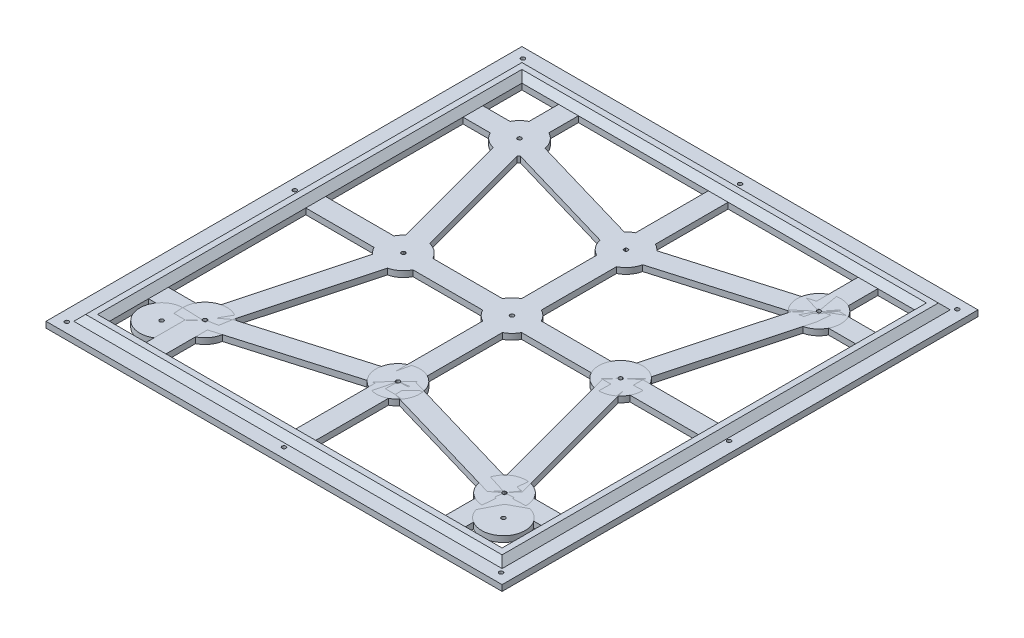
SolidWorks part; units mm, degrees
ref_plane "Front Plane" through (0, 0, 0) normal (0, 0, 1) x (1, 0, 0)
ref_plane "Top Plane" through (0, 0, 0) normal (0, 1, 0) x (1, 0, 0)
ref_plane "Right Plane" through (0, 0, 0) normal (1, 0, 0) x (0, 0, -1)
sketch "Sketch1" plane through (0, 0, 0) normal (0, 1, 0) x (1, 0, 0)
  line L1 (-115, 120) -> (115, 120)
  line L2 (-115, 120) -> (-115, -120)
  line L3 (-115, -120) -> (115, -120)
  line L4 (115, 120) -> (115, -120)
  line L5 (-115, 120) -> (115, -120) construction
  line L6 (-115, -120) -> (115, 120) construction
  point P0 (0, 0)
  dimension "D1" = 240
  dimension "D2" = 230
extrude "Boss-Extrude1" add sketch "Sketch1" along normal blind 3
sketch "Sketch2" plane through (0, 3, 0) normal (0, 1, 0) x (1, 0, 0)
  line L0 (0, -115) -> (0, 0) construction
  line L5 (-109.5, 115) -> (109.5, 115) construction
  line L7 (-109.5, 115) -> (-109.5, -115) construction
  line L8 (-109.5, -115) -> (109.5, -115) construction
  line L9 (115, -120) -> (115, 120)
  line L11 (115, 120) -> (-115, 120)
  line L13 (-115, 120) -> (-115, -120)
  line L15 (-115, -120) -> (115, -120)
  line L16 (115, -120) -> (115, 120) construction
  line L17 (115, 120) -> (-115, 120) construction
  line L18 (-115, 120) -> (-115, -120) construction
  line L19 (-115, -120) -> (115, -120) construction
  line L20 (109.5, 115) -> (109.5, -115) construction
  line L21 (-109.5, 115) -> (109.5, -115) construction
  line L22 (-109.5, -115) -> (109.5, 115) construction
  line L23 (-109.5, 0) -> (0, 0) construction
  line L24 (0, 0) -> (109.5, 0) construction
  line L25 (0, 0) -> (0, 115) construction
  circle A0 centre (0, 0) radius 125 construction
  circle A1 centre (-109.5, -115) radius 1
  circle A2 centre (109.5, -115) radius 1
  circle A3 centre (0, -115) radius 1
  circle A4 centre (-86.1971, -90.5266) radius 1
  circle A5 centre (86.1971, -90.5266) radius 1
  circle A6 centre (0, 0) radius 1
  circle A7 centre (-109.5, 0) radius 1
  circle A8 centre (-109.5, 115) radius 1
  circle A9 centre (-75.5086, 79.3013) radius 1
  circle A10 centre (75.5086, 79.3013) radius 1
  circle A11 centre (0, 115) radius 1
  circle A12 centre (109.5, 115) radius 1
  circle A13 centre (109.5, 0) radius 1
  circle A14 centre (0, 57.5) radius 1
  circle A15 centre (0, -57.5) radius 1
  circle A16 centre (-54.75, 0) radius 1
  circle A17 centre (54.75, 0) radius 1
  circle A19 centre (0, 0) radius 109.5 construction
  circle A20 centre (-75.5086, -79.3013) radius 1
  circle A21 centre (75.5086, -79.3013) radius 1
  point P2 (0, 0)
  point P46 (0, 0)
  point P47 (0, 0)
  dimension "D1" = 0
  dimension "D2" = 219
  dimension "D3" = 5
  dimension "D4" = 2
  dimension "D5" = 240
  dimension "D6" = 24.4734
  dimension "D7" = 250
extrude "Cut-Extrude1" cut sketch "Sketch2" against normal up to next
sketch "Sketch4" plane through (0, 3, 0) normal (0, 1, 0) x (1, 0, 0)
  line L12 (115, -120) -> (115, 120)
  line L13 (115, 120) -> (-115, 120)
  line L14 (-115, 120) -> (-115, -120)
  line L15 (-115, -120) -> (115, -120)
  line L16 (115, -120) -> (115, 120) construction
  line L17 (115, 120) -> (-115, 120) construction
  line L18 (-115, 120) -> (-115, -120) construction
  line L19 (-115, -120) -> (115, -120) construction
  line L24 (105, -110) -> (105, 110)
  line L25 (105, 110) -> (-105, 110)
  line L26 (-105, 110) -> (-105, -110)
  line L27 (-105, -110) -> (105, -110)
  line L28 (105, -110) -> (105, 110)
  line L29 (105, 110) -> (-105, 110)
  line L30 (-105, 110) -> (-105, -110)
  line L31 (-105, -110) -> (105, -110)
  line L36 (102, -107) -> (102, 107)
  line L37 (102, 107) -> (-102, 107)
  line L38 (-102, 107) -> (-102, -107)
  line L39 (-102, -107) -> (102, -107)
  line L40 (102, -107) -> (102, 107)
  line L41 (102, 107) -> (-102, 107)
  line L42 (-102, 107) -> (-102, -107)
  line L43 (-102, -107) -> (102, -107)
  dimension "D1" = 0
  dimension "D2" = 10
  dimension "D3" = 13
extrude "Boss-Extrude2" add sketch "Sketch4" along normal blind 3
chamfer "Chamfer1" distance 3 angle 45 8 edges at (0, 3, -110) (105, 3, 0) (0, 3, 110) (-105, 3, 0) (0, 3, -107) (102, 3, 0) (0, 3, 107) (-102, 3, 0)
sketch "Sketch5" plane through (0, 3, 0) normal (0, 1, 0) x (1, 0, 0)
  line L8 (99, -104) -> (99, 104)
  line L9 (99, 104) -> (-99, 104)
  line L10 (-99, 104) -> (-99, -104)
  line L11 (-99, -104) -> (99, -104)
  line L12 (99, -104) -> (99, 104)
  line L13 (99, 104) -> (-99, 104)
  line L14 (-99, 104) -> (-99, -104)
  line L15 (-99, -104) -> (99, -104)
  circle A0 centre (0, 0) radius 1 construction
  circle A1 centre (0, 0) radius 1 construction
  circle A2 centre (0, 0) radius 11
  circle A4 centre (75.5086, 79.3013) radius 11
  circle A5 centre (54.75, 0) radius 11
  circle A6 centre (-54.75, 0) radius 11
  circle A7 centre (0, -57.5) radius 11
  circle A8 centre (0, 57.5) radius 11
  circle A9 centre (-75.5086, 79.3013) radius 11
  circle A10 centre (86.1971, -90.5266) radius 11
  circle A11 centre (-86.1971, -90.5266) radius 11
  circle A12 centre (75.5086, -79.3013) radius 1 construction
  circle A13 centre (-75.5086, -79.3013) radius 1 construction
  circle A14 centre (75.5086, -79.3013) radius 1 construction
  circle A15 centre (-75.5086, -79.3013) radius 1 construction
  circle A16 centre (-75.5086, -79.3013) radius 11
  circle A17 centre (75.5086, -79.3013) radius 11
  circle A26 centre (75.5086, 79.3013) radius 1
  circle A27 centre (75.5086, 79.3013) radius 1 construction
  circle A28 centre (54.75, 0) radius 1
  circle A29 centre (54.75, 0) radius 1 construction
  circle A30 centre (-54.75, 0) radius 1
  circle A31 centre (-54.75, 0) radius 1 construction
  circle A32 centre (0, -57.5) radius 1
  circle A33 centre (0, -57.5) radius 1 construction
  circle A34 centre (0, 57.5) radius 1
  circle A35 centre (0, 57.5) radius 1 construction
  circle A36 centre (-75.5086, 79.3013) radius 1
  circle A37 centre (-75.5086, 79.3013) radius 1 construction
  circle A38 centre (86.1971, -90.5266) radius 1
  circle A39 centre (86.1971, -90.5266) radius 1 construction
  circle A40 centre (-86.1971, -90.5266) radius 1
  circle A41 centre (-86.1971, -90.5266) radius 1 construction
  dimension "D5" = 0
  dimension "D1" = 0
  dimension "D3" = 0
  dimension "D2" = 0
  dimension "D4" = 0
  dimension "D6" = 0
  dimension "D7" = 0
  dimension "D8" = 0
  dimension "D9" = 10
  dimension "D10" = 0
  dimension "D11" = 10
extrude "Cut-Extrude2" cut sketch "Sketch5" against normal up to next contours L14 L15 L12 L13 A17 A10 A16 A11 A9 A8 A7 A6 A5 A4 A2 region at (0, 3, 101.1283)
sketch "Sketch6" plane through (0, 3, 0) normal (0, 1, 0) x (1, 0, 0)
  line L0 (-55.75, 0) -> (-99, 0)
  line L1 (-99, 104) -> (-99, -104) construction
  line L2 (-74.5489, 79.0205) -> (-1, 57.5)
  line L3 (-75.5086, 78.3013) -> (-54.75, 1)
  line L4 (1, 57.5) -> (-1, 57.5) construction
  line L5 (0, 56.5) -> (0, 1)
  line L6 (75.5086, 79.3013) -> (75.5086, 78.3013) construction
  line L7 (54.75, 1) -> (54.75, -1) construction
  line L8 (-76.5086, 79.3013) -> (-99, 79.3013)
  line L9 (-75.5086, 80.3013) -> (-75.5086, 104)
  line L10 (99, 104) -> (-99, 104) construction
  line L11 (53.75, 0) -> (1, 0)
  line L12 (-54.75, 1) -> (-54.75, -1) construction
  line L13 (-75.5086, 79.3013) -> (-75.5086, 78.3013) construction
  line L14 (75.5086, 80.3013) -> (75.5086, 104)
  line L15 (76.5086, 79.3013) -> (99, 79.3013)
  line L16 (75.5086, 78.3013) -> (54.75, 1)
  line L17 (74.5489, 79.0205) -> (1, 57.5)
  line L18 (0, 58.5) -> (0, 104)
  line L19 (55.75, 0) -> (99, 0)
  line L20 (-53.75, 0) -> (-1, 0)
  line L21 (-75.5086, -79.3013) -> (-75.5086, -78.3013) construction
  line L22 (75.5086, -79.3013) -> (75.5086, -78.3013) construction
  line L23 (1, -57.5) -> (-1, -57.5) construction
  line L24 (0, -58.5) -> (0, -104)
  line L25 (74.5489, -79.0205) -> (1, -57.5)
  line L26 (75.5086, -78.3013) -> (54.75, -1)
  line L27 (76.5086, -79.3013) -> (99, -79.3013)
  line L28 (75.5086, -80.3013) -> (75.5086, -104)
  line L29 (-75.5086, -80.3013) -> (-75.5086, -104)
  line L30 (-76.5086, -79.3013) -> (-99, -79.3013)
  line L31 (0, -56.5) -> (0, -1)
  line L32 (-75.5086, -78.3013) -> (-54.75, -1)
  line L33 (-74.5489, -79.0205) -> (-1, -57.5)
  circle A6 centre (-75.5086, 79.3013) radius 1 construction
  circle A7 centre (0, 57.5) radius 1 construction
  circle A9 centre (-54.75, 0) radius 1 construction
  circle A10 centre (0, 0) radius 1 construction
  point P12 (0, 57.5)
  point P40 (-54.75, 0)
  point P41 (54.75, 0)
  point P69 (0, -57.5)
extrude "Extrude-Thin2" add sketch "Sketch6" against normal up to surface (3 mm away) thin up to face at (75.5086, 0, -78.3013) thin type mid plane wall 10
